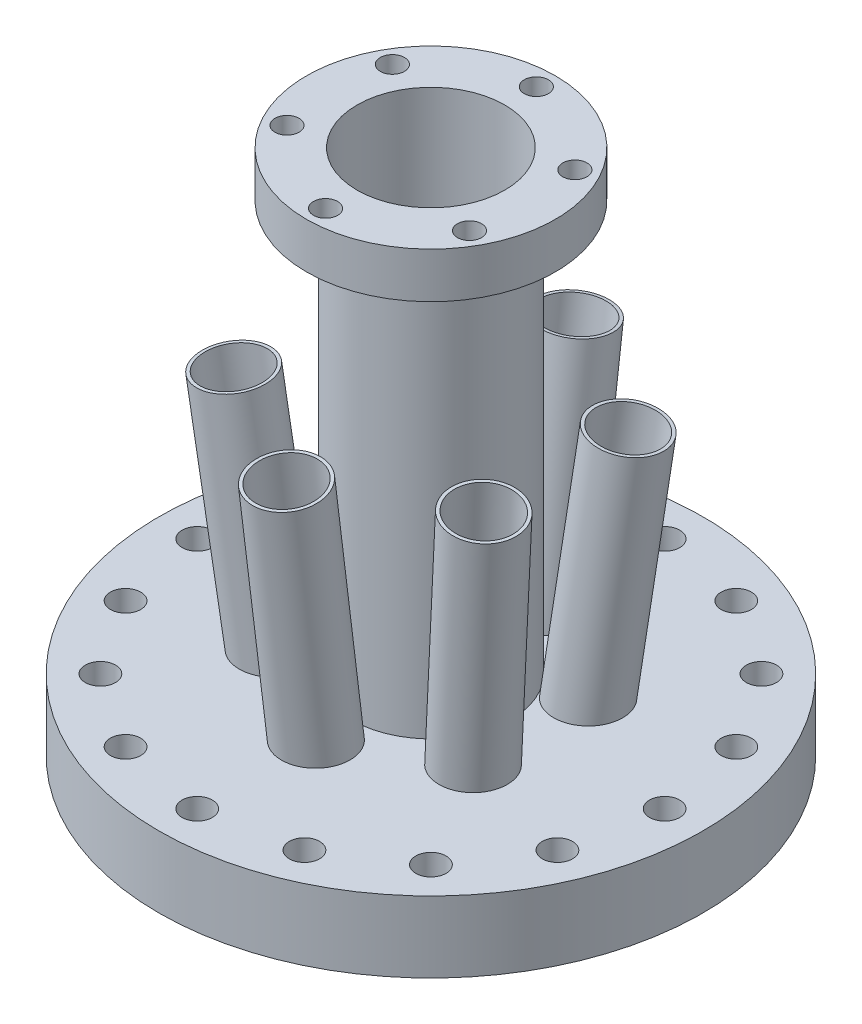
SolidWorks part; units mm, degrees
ref_plane "Front Plane" through (0, 0, 0) normal (0, 0, 1) x (1, 0, 0)
ref_plane "Top Plane" through (0, 0, 0) normal (0, 1, 0) x (1, 0, 0)
ref_plane "Right Plane" through (0, 0, 0) normal (1, 0, 0) x (0, 0, -1)
sketch "Sketch1" plane through (0, 0, 0) normal (0, 1, 0) x (1, 0, 0)
  circle A0 centre (0, 0) radius 75.819
  dimension "D1" = 151.638
extrude "Extrude1" add sketch "Sketch1" along normal blind 19.812
sketch "Sketch2" plane through (0, 19.812, 0) normal (0, 1, 0) x (1, 0, 0)
  line L0 (0, 0) -> (0, 65.1256) construction
  circle A0 centre (0, 65.1256) radius 4.2164
  dimension "D1" = 8.4328
  dimension "D2" = 65.1256
extrude "Extrude2" cut sketch "Sketch2" against normal blind 19.812
pattern_circular "CirPattern1" count 16 over 360 about axis through (0, 19.812, 0) along (0, -1, 0) of "Extrude2"
sketch "Sketch3" plane through (0, 19.812, 0) normal (0, 1, 0) x (1, 0, 0)
  circle A0 centre (0, 0) radius 22.225
  circle A1 centre (0, 0) radius 20.574
  dimension "D1" = 44.45
  dimension "D2" = 41.148
extrude "Extrude3" add sketch "Sketch3" along normal blind 127
sketch "Sketch4" plane through (0, 19.812, 0) normal (0, 1, 0) x (1, 0, 0)
  circle A0 centre (0, 0) radius 20.574
extrude "Extrude4" cut sketch "Sketch4" against normal up to next
sketch "Sketch6" plane through (0, 146.812, 0) normal (0, 1, 0) x (1, 0, 0)
  circle A0 centre (0, 0) radius 20.574
  circle A1 centre (0, 0) radius 34.671
  dimension "D1" = 69.342
extrude "Extrude5" add sketch "Sketch6" against normal blind 12.7
sketch "Sketch7" plane through (0, 146.812, 0) normal (0, 1, 0) x (1, 0, 0)
  line L0 (0, 0) -> (0, 29.3624) construction
  circle A0 centre (0, 29.3624) radius 3.3655
  dimension "D1" = 6.731
  dimension "D2" = 29.3624
extrude "Extrude6" cut sketch "Sketch7" against normal up to next
pattern_circular "CirPattern2" count 6 over 360 about axis through (0, 134.112, 0) along (0, 1, 0) of "Extrude6"
ref_plane "Plane1" through (0, -241.3, 0) normal (0, 1, 0) x (-1, 0, 0)
sketch "Sketch8" plane through (0, -241.3, 0) normal (0, 1, 0) x (-1, 0, 0)
  point P0 (0, 0)
sketch "Sketch9" plane through (0, 0, 0) normal (1, 0, 0) x (0, 0, -1)
  line L0 (0, -241.3) -> (-36.4102, 55.2376) construction
  line L1 (0, -241.3) -> (0, 105.0487) construction
  dimension "D1" = 7
ref_plane "Plane2" through (0, -241.3, 0) normal (0, 0.9925, 0.1219) x (-1, 0, 0)
sketch "Sketch10" plane through (0, -241.3, 0) normal (0, 0.9925, 0.1219) x (-1, 0, 0)
  circle A0 centre (0, 0) radius 9.525
  circle A1 centre (0, 0) radius 8.636
  dimension "D1" = 19.05
  dimension "D2" = 17.272
extrude "Extrude7" add sketch "Sketch10" along normal blind 330.2
extrude "Extrude8" cut sketch "Sketch10<2>" along normal up to surface (244.2816 mm away) up to face at (-23.3089, 0, -56.2728)
sketch "Sketch10<2>" plane through (0, -241.3, 0) normal (0, 0.9925, 0.1219) x (-1, 0, 0) same geometry as "Sketch10"
sketch "Sketch11" plane through (0, -241.3, 0) normal (0, 0.9925, 0.1219) x (-1, 0, 0)
  circle A0 centre (0, 0) radius 8.636
  circle A1 centre (0, 0) radius 8.636 construction
extrude "Extrude9" cut sketch "Sketch11" along normal through all
pattern_circular "CirPattern3" count 6 over 360 about axis through (0, 19.812, 0) along (0, -1, 0) of "Extrude7", "Extrude8", "Extrude9"
